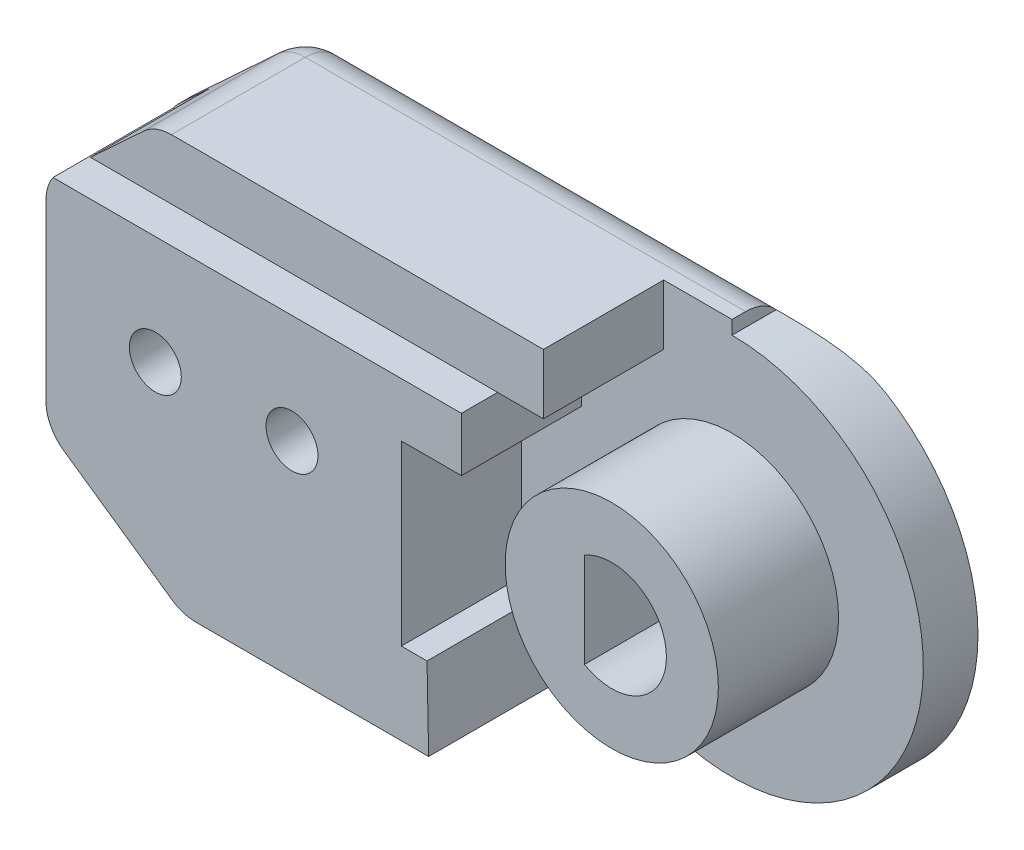
SolidWorks part; units mm, degrees
ref_plane "Front Plane" through (0, 0, 0) normal (0, 0, 1) x (1, 0, 0)
ref_plane "Top Plane" through (0, 0, 0) normal (0, 1, 0) x (1, 0, 0)
ref_plane "Right Plane" through (0, 0, 0) normal (1, 0, 0) x (0, 0, -1)
sketch "Sketch2" plane through (0, 0, 0) normal (0, 0, 1) x (1, 0, 0)
  line L1 (-2.5, 7.5) -> (-16.7, 7.5)
  line L2 (-20.7, 3.7934) -> (-20.7, -4.0316)
  line L3 (-15.7, -7.5) -> (-6.7, -7.5)
  line L4 (-6.7, -7.5) -> (-4.2, -5.6)
  line L5 (-2.5, 7.5) -> (0, 7.5)
  line L7 (0, 7) -> (0, 7.5)
  line L8 (-20.7, 3.7934) -> (-16.7, 7.5)
  line L9 (-20.7, -4.0316) -> (-15.7, -7.5)
  arc A1 (-4.2, -5.6) -> (7, 0) centre (0, 0) ccw
  arc A2 (7, 0) -> (0, 7) centre (0, 0) ccw
  dimension "D1" = 7
  dimension "D2" = 4
  dimension "D3" = 5
  dimension "D4" = 7.5
  dimension "D5" = 15
  dimension "D7" = 2.5
  dimension "D8" = 14
extrude "Boss-Extrude1" add sketch "Sketch2" along normal blind 2 contours A1 A2 L7 L5 L1 L8 L2 L9 L3 L4
sketch "Sketch4" plane through (0, 0, 2) normal (0, 0, 1) x (1, 0, 0)
  line L7 (-15.7, -7.5) -> (-6.7, -7.5)
  line L8 (-6.7, -7.5) -> (-6.7591, -4.5)
  line L9 (-6.7591, -4.5) -> (-7.7, -4.5)
  line L10 (-16.7, 7.5) -> (-2.5, 7.5)
  line L13 (-5.5, 2) -> (-5.5, 5.3)
  line L14 (-5.5, 5.3) -> (-2.5, 5.3)
  line L21 (-20.7, -4.0316) -> (-15.7, -7.5)
  line L24 (-16.7, 7.5) -> (-20.7, 3.7934)
  line L25 (-20.7, -4.0316) -> (-20.7, 3.7934)
  line L26 (-7.7, 2) -> (-5.5, 2)
  line L29 (-7.7, 2) -> (-7.7, -4.5)
  line L30 (-2.5, 7.5) -> (-2.5, 5.3)
  point P2 (-5.5, 3.65)
  dimension "D1" = 13
  dimension "D2" = 2.5
  dimension "D3" = 3
  dimension "D4" = 3
extrude "Boss-Extrude2" add sketch "Sketch4" along normal blind 8
ref_point "Point1"
sketch "Sketch22" plane through (0, 0, 2) normal (0, 0, 1) x (1, 0, 0)
  line L0 (0, 5.3) -> (-14, 5.3) construction
  line L1 (0, 4) -> (-14, 4) construction
  line L2 (-14, 4) -> (-14, 5.3) construction
  circle A0 centre (0, 0) radius 5.3 construction
  circle A1 centre (0, 0) radius 4 construction
  dimension "D1" = 14
  dimension "D2" = 10.6
  dimension "D3" = 8
sketch "Sketch24" plane through (0, 0, 2) normal (0, 0, 1) x (1, 0, 0)
  circle A0 centre (0, 0) radius 3.9
  dimension "D1" = 7.8
extrude "Boss-Extrude5" add sketch "Sketch24" along normal blind 4.4
sketch "Sketch29" plane through (-5.5, 0, 0) normal (1, 0, 0) x (0, 0, -1)
  line L0 (-1.9279, 3.9758) -> (-10, 3.9758) construction
  line L1 (-10, 2) -> (-10, 5.3) construction
sketch "Sketch30" plane through (-5.5, 0, 0) normal (1, 0, 0) x (0, 0, -1)
  line L0 (-6.4086, 3.9758) -> (-6.4086, 5.3)
  line L1 (-6.4086, 3.9758) -> (-2, 3.9758)
  line L2 (-6.4086, 5.3) -> (-2, 5.3)
  line L3 (-2, 3.9758) -> (-2, 5.3)
  line L6 (-2, 2) -> (-2, 5.3) construction
  line L7 (-10, 5.3) -> (-2, 5.3) construction
  point P0 (-4.4086, 5.3)
  point P6 (0, 0)
  point P8 (0, 0)
  point P9 (0, 0)
  dimension "D1" = 4.4086
extrude "Cut-Extrude12" cut sketch "Sketch30" against normal blind 16
ref_plane "Plane1" through (0, 0, 10) normal (0, 0, 1) x (1, 0, 0)
sketch "Sketch8" plane through (0, 0, 2) normal (0, 0, 1) x (1, 0, 0)
  circle A1 centre (0, 0) radius 3.8
  circle A2 centre (0, 0) radius 2.5
sketch "Sketch28" plane through (0, 0, 6.4) normal (0, 0, 1) x (1, 0, 0)
  line L0 (-1, 1.7321) -> (-1, -1.7321)
  arc A0 (-1, -1.7321) -> (-1, 1.7321) centre (0, 0) ccw
  dimension "D1" = 1
  dimension "D2" = 2
extrude "Cut-Extrude11" cut sketch "Sketch28" against normal through all
sketch "Sketch33" plane through (0, 0, 10) normal (0, 0, 1) x (1, 0, 0)
  line L0 (-7, 2) -> (-0.5657, -5.1566) construction
  line L2 (-8.2591, -4.5) -> (-2.6001, 3.0469) construction
  dimension "D1" = 1.5
  dimension "D2" = 1.5
fillet "Fillet1" radius 1.5 9 edges at (-11.2, -7.5, 0) (-8.35, 7.5, 0) (-18.7, 5.6467, 0) (-18.2, -5.7658, 0) (-20.7, -0.1191, 0) (-15.7, -7.5, 5) (-20.7, -4.0316, 5) (-20.7, 3.7934, 5) (-16.7, 7.5, 5)
sketch "Sketch34" plane through (0, 2, 0) normal (0, -1, 0) x (1, 0, 0)
  line L0 (-5.5, 1.9279) -> (-5.5, 10) construction
  line L1 (8.25, 10) -> (-8.25, 10) construction
  circle A0 centre (-7, 10) radius 0.75
  point P2 (0, 0)
  dimension "D1" = 1.5
  dimension "D2" = 1.5
extrude "Cut-Extrude13" cut sketch "Sketch34" along direction (0.6686, -0.7436, 0) on the side against the normal blind 8
sketch "Sketch35" plane through (0, -4.5, 0) normal (0, 1, 0) x (1, 0, 0)
  circle A0 centre (-8.2591, -10) radius 0.75
extrude "Cut-Extrude14" cut sketch "Sketch35" along direction (0.5999, 0.8001, 0) on the side against the normal blind 8 and the other way blind 3
sketch "Sketch36" plane through (0, 0, 10) normal (0, 0, 1) x (1, 0, 0)
  line L2 (-7.7, -2.7542) -> (-7.7, 2) construction
  circle A0 centre (-11.7, 0) radius 0.95
  circle A1 centre (-16.7, 0) radius 0.95
  dimension "D1" = 4
  dimension "D2" = 5
extrude "Cut-Extrude15" cut sketch "Sketch36" against normal blind 8
sketch "Sketch37" plane through (0, 0, 0) normal (0, 0, -1) x (-1, 0, 0)
  circle A0 centre (11.7, 0) radius 2
  circle A1 centre (16.7, 0) radius 2
extrude "Cut-Extrude16" cut sketch "Sketch37" against normal blind 4.5
sketch "Sketch38" plane through (0, 0, 10) normal (0, 0, 1) x (1, 0, 0)
  line L0 (-5.5, 5.3) -> (-2.5, 5.3)
  line L1 (-5.5, 5.3) -> (-5.5, 6.55)
  line L2 (-2.5, 5.3) -> (-2.5, 6.55)
  line L3 (-5.5, 6.55) -> (-2.5, 6.55)
  dimension "D1" = 1.25
extrude "Cut-Extrude17" cut sketch "Sketch38" against normal blind 3.6
ref_plane "Plane2" through (0, 0, 6.4) normal (0, 0, 1) x (1, 0, 0)
split "Split1" trim tools "Plane2" bodies to split 129 resulting bodies 130 131
delete or keep bodies "Body-Delete/Keep 1" type delete bodies bodies 130
